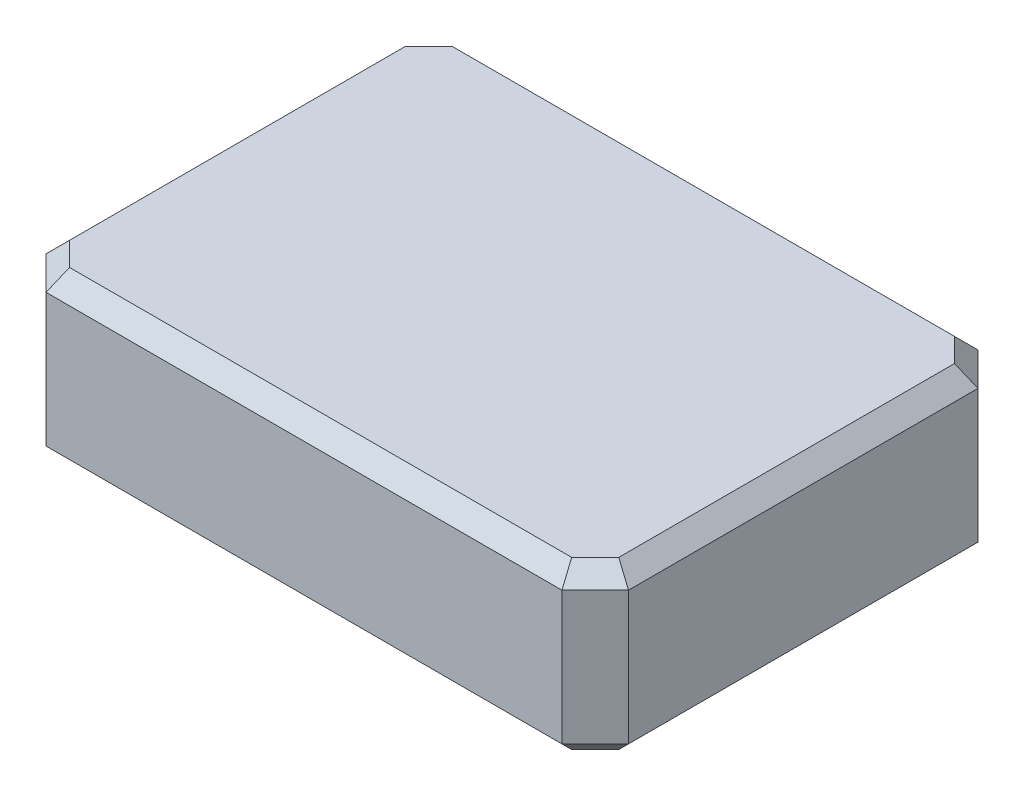
SolidWorks part; units mm, degrees
ref_plane "Front Plane" through (0, 0, 0) normal (0, 0, 1) x (1, 0, 0)
ref_plane "Top Plane" through (0, 0, 0) normal (0, 1, 0) x (1, 0, 0)
ref_plane "Right Plane" through (0, 0, 0) normal (1, 0, 0) x (0, 0, -1)
ref_axis "X" through (-88.99, 0, 0) along (1, 0, 0)
ref_axis "Y" through (0, 55, 0) along (0, -1, 0)
ref_axis "Z" through (0, 0, -88.99) along (0, 0, 1)
sketch "Sketch1" plane through (0, 0, 0) normal (0, 1, 0) x (1, 0, 0)
  line L1 (-175, 125) -> (175, 125)
  line L2 (-175, 125) -> (-175, -125)
  line L3 (-175, -125) -> (175, -125)
  line L4 (175, 125) -> (175, -125)
  line L5 (-175, 125) -> (175, -125) construction
  line L6 (-175, -125) -> (175, 125) construction
  point P0 (0, 0)
  dimension "D1" = 250
  dimension "D2" = 350
extrude "Boss-Extrude1" add sketch "Sketch1" along normal mid plane 100
chamfer "Chamfer1" distance 20 angle 45 4 edges at (-175, 0, -125) (-175, 0, 125) (175, 0, -125) (175, 0, 125)
chamfer "Chamfer2" distance 10 angle 45 16 edges at (165, 50, -115) (175, 50, 0) (165, 50, 115) (0, 50, 125) (-165, 50, 115) (-175, 50, 0) (-165, 50, -115) (0, 50, -125) (-165, -50, 115) (0, -50, 125) (165, -50, 115) (175, -50, 0) (165, -50, -115) (0, -50, -125) (-165, -50, -115) (-175, -50, 0)
